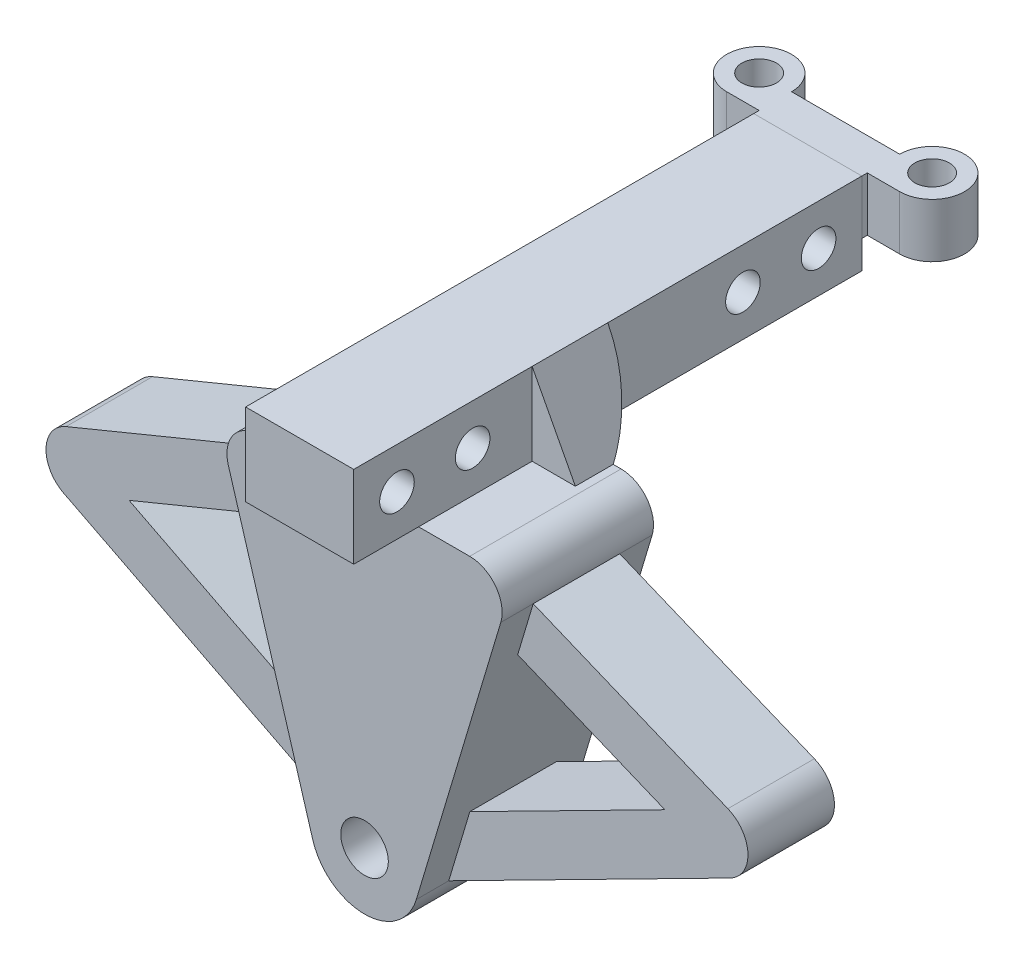
SolidWorks part; units mm, degrees
ref_plane "前视基准面" through (0, 0, 0) normal (0, 0, 1) x (1, 0, 0)
ref_plane "上视基准面" through (0, 0, 0) normal (0, 1, 0) x (1, 0, 0)
ref_plane "右视基准面" through (0, 0, 0) normal (1, 0, 0) x (0, 0, -1)
sketch "草图1" plane through (0, 0, 0) normal (1, 0, 0) x (0, 0, -1)
  line L0 (0, 0) -> (-23.5, 0) construction
  line L1 (23.5, -3.8) -> (-23.5, -3.8)
  line L2 (23.5, -3.8) -> (23.5, 3.8)
  line L3 (23.5, 3.8) -> (-23.5, 3.8)
  line L4 (-23.5, -3.8) -> (-23.5, 3.8)
  line L5 (23.5, -3.8) -> (-23.5, 3.8) construction
  line L6 (23.5, 3.8) -> (-23.5, -3.8) construction
  line L7 (0, 0) -> (0, -7.5593) construction
  circle A0 centre (-19.5, 0) radius 1.6
  circle A1 centre (-12.5, 0) radius 1.6
  circle A4 centre (12.5, 0) radius 1.6
  circle A5 centre (19.5, 0) radius 1.6
  point P0 (0, 0)
  dimension "D1" = 47
  dimension "D2" = 7.6
  dimension "D3" = 7
  dimension "D4" = 12.5
extrude "凸台-拉伸1" add sketch "草图1" along normal mid plane 10
sketch "草图4" plane through (0, 0, 0) normal (0, 0, 1) x (1, 0, 0)
  line L0 (0, 0) -> (0, 7.8238) construction
  line L2 (5, 3.8) -> (5, -3.8)
  line L3 (5, -3.8) -> (9, -3.8)
  line L6 (-5, -3.8) -> (-9, -3.8)
  line L7 (-5, 3.8) -> (-5, -3.8)
  line L9 (-5, 3.8) -> (-9, -3.8)
  line L10 (5, 3.8) -> (9, -3.8)
extrude "凸台-拉伸3" add sketch "草图4" along normal blind 7
ref_plane "基准面1" through (0, 0, 10.5) normal (0, 0, 1) x (1, 0, 0)
sketch "草图3" plane through (0, 0, 10.5) normal (0, 0, 1) x (1, 0, 0)
  line L0 (0, -3.8) -> (0, -9.8882) construction
  line L2 (0, -3.8) -> (-13.7569, -3.8)
  line L3 (5, -3.8) -> (-5, -3.8) construction
  line L4 (-13.7569, -3.8) -> (0, -49.7667)
  line L5 (0, -49.7667) -> (13.7569, -3.8)
  line L6 (13.7569, -3.8) -> (0, -3.8)
  circle A0 centre (0, -32.0203) radius 2.2
extrude "凸台-拉伸2" add sketch "草图3" along normal mid plane 14
fillet "圆角1" radius 5 1 edges at (0, -49.7667, 10.5)
fillet "圆角2" radius 3 2 edges at (-13.7569, -3.8, 10.5) (13.7569, -3.8, 10.5)
fillet "圆角4" radius 10 2 edges at (-7, -3.8, 0) (7, -3.8, 0)
sketch "草图5" plane through (0, 0, 10.5) normal (0, 0, 1) x (1, 0, 0)
  line L0 (-12.6016, -7.6601) -> (-36.6477, -17.5625)
  line L1 (-36.6477, -17.5625) -> (-4.7901, -33.7614)
  line L2 (-12.6016, -7.6601) -> (-11.1642, -12.4632)
  line L3 (-24.7828, -18.0714) -> (-11.1642, -12.4632)
  line L4 (-24.7828, -18.0714) -> (-6.7401, -27.2457)
  line L5 (-6.7401, -27.2457) -> (-4.7901, -33.7614)
  line L6 (-12.6016, -7.6601) -> (-4.7901, -33.7614) construction
extrude "凸台-拉伸4" add sketch "草图5" along normal mid plane 8
fillet "圆角3" radius 3 1 edges at (-36.6477, -17.5625, 10.5)
mirror "镜向1" about plane through (0, 0, 0) normal (1, 0, 0) of "圆角3", "凸台-拉伸4"
sketch "草图6" plane through (0, 3.8, 0) normal (0, 1, 0) x (1, 0, 0)
  line L0 (-5, 23.5) -> (-5, 24)
  line L1 (-5, 24) -> (-8, 24)
  line L11 (5, 23.5) -> (-5, 23.5)
  line L12 (0, 23.5) -> (0, 32.0606) construction
  line L13 (-5, 27) -> (5, 27)
  line L15 (5, 24) -> (8, 24)
  line L16 (5, 23.5) -> (5, 24)
  circle A0 centre (-8, 27) radius 1.6
  arc A2 (-5, 27) -> (-8, 24) centre (-8, 27) ccw
  arc A3 (5, 27) -> (8, 24) centre (8, 27) cw
  circle A4 centre (8, 27) radius 1.6
  dimension "D2" = 3
  dimension "D1" = 8
  dimension "D3" = 0.5
extrude "凸台-拉伸5" add sketch "草图6" against normal blind 5 separate body
